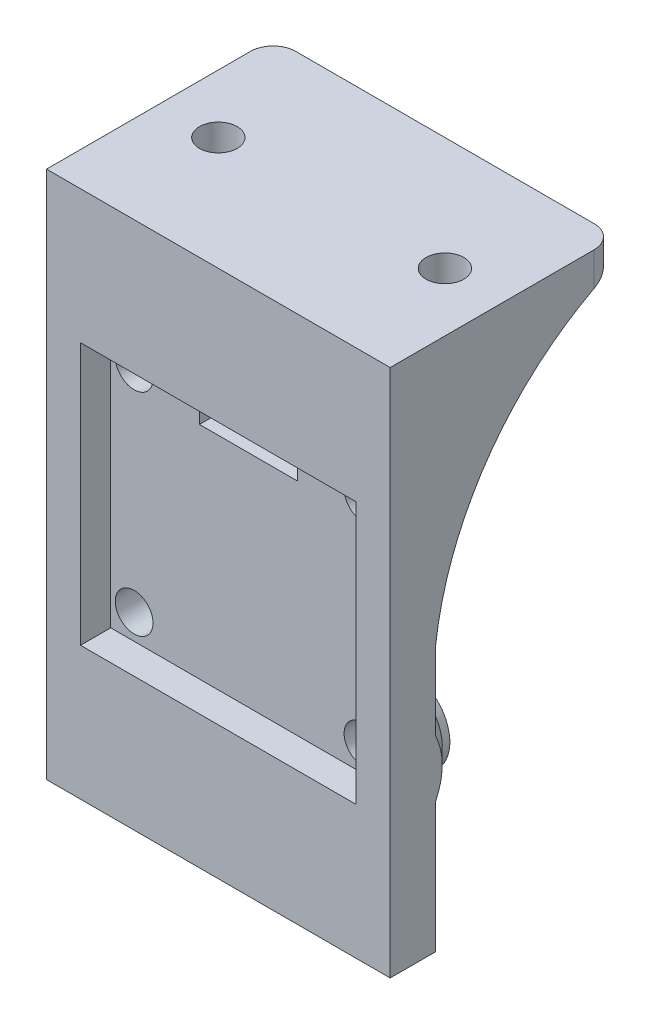
SolidWorks part; units mm, degrees
material "ABS"
ref_plane "Front Plane" through (0, 0, 0) normal (0, 0, 1) x (1, 0, 0)
ref_plane "Top Plane" through (0, 0, 0) normal (0, 1, 0) x (1, 0, 0)
ref_plane "Right Plane" through (0, 0, 0) normal (1, 0, 0) x (0, 0, -1)
sketch "Sketch1" plane through (0, 0, 0) normal (0, 0, 1) x (1, 0, 0)
  line L1 (-22.75, -35) -> (22.75, -35)
  line L2 (-22.75, -35) -> (-22.75, 35)
  line L3 (-22.75, 35) -> (22.75, 35)
  line L4 (22.75, -35) -> (22.75, 35)
  line L5 (-22.75, -35) -> (22.75, 35) construction
  line L6 (-22.75, 35) -> (22.75, -35) construction
  line L7 (-15.15, -14) -> (15.15, -14) construction
  line L8 (-15.15, -14) -> (-15.15, 14) construction
  line L9 (-15.15, 14) -> (15.15, 14) construction
  line L10 (15.15, -14) -> (15.15, 14) construction
  line L11 (-15.15, -14) -> (15.15, 14) construction
  line L12 (-15.15, 14) -> (15.15, -14) construction
  circle A0 centre (-15.15, 14) radius 2.5
  circle A1 centre (15.15, 14) radius 2.5
  circle A2 centre (15.15, -14) radius 2.5
  circle A3 centre (-15.15, -14) radius 2.5
  point P0 (0, 0)
  point P5 (0, 0)
  dimension "D5" = 5
  dimension "D1" = 70
  dimension "D2" = 45.5
  dimension "D3" = 28
  dimension "D4" = 30.3
extrude "Boss-Extrude1" add sketch "Sketch1" along normal blind 6
sketch "Sketch2" plane through (0, 0, 6) normal (0, 0, 1) x (1, 0, 0)
  line L1 (18.25, 17.35) -> (-18.25, 17.35)
  line L2 (18.25, 17.35) -> (18.25, -17.35)
  line L3 (18.25, -17.35) -> (-18.25, -17.35)
  line L4 (-18.25, 17.35) -> (-18.25, -17.35)
  line L5 (18.25, 17.35) -> (-18.25, -17.35) construction
  line L6 (18.25, -17.35) -> (-18.25, 17.35) construction
  point P0 (0, 0)
  dimension "D1" = 34.7
  dimension "D2" = 36.5
extrude "Cut-Extrude1" cut sketch "Sketch2" against normal blind 4
sketch "Sketch3" plane through (0, 0, 0) normal (1, 0, 0) x (0, 0, -1)
  line L0 (0, 35) -> (24, 35)
  line L1 (24, 35) -> (24, 32)
  line L2 (24, 32) -> (0, 32)
  line L3 (0, 35) -> (0, -35) construction
  line L4 (0, 32) -> (0, 35)
  dimension "D1" = 3
  dimension "D2" = 24
extrude "Boss-Extrude2" add sketch "Sketch3" along normal through all and the other way through all
sketch "Sketch4" plane through (-22.75, 0, 0) normal (-1, 0, 0) x (0, 0, 1)
  line L0 (-24, 32) -> (0, 32)
  line L1 (0, 32) -> (0, 0)
  arc A0 (-24, 32) -> (0, 0) centre (-39.7128, -4.7846) cw
  dimension "D1" = 40
extrude "Boss-Extrude3" add sketch "Sketch4" against normal blind 2
sketch "Sketch5" plane through (22.75, 0, 0) normal (1, 0, 0) x (0, 0, -1)
  line L2 (24, 32) -> (0, 32)
  line L3 (0, 32) -> (0, 0)
  line L4 (24, 32) -> (0, 32)
  line L5 (0, 32) -> (0, 0)
  arc A1 (24, 32) -> (0, 0) centre (39.7128, -4.7846) ccw
  arc A2 (24, 32) -> (0, 0) centre (39.7128, -4.7846) ccw
  dimension "D1" = 0
extrude "Boss-Extrude4" add sketch "Sketch5" against normal blind 2
sketch "Sketch6" plane through (0, 35, 0) normal (0, 1, 0) x (1, 0, 0)
  line L0 (15, 9) -> (-15, 9) construction
  line L3 (0, 0) -> (0, 9) construction
  circle A0 centre (-15, 9) radius 2.5
  circle A1 centre (15, 9) radius 2.5
  point P3 (0, 9)
  dimension "D3" = 5
  dimension "D1" = 9
  dimension "D2" = 30
extrude "Cut-Extrude2" cut sketch "Sketch6" against normal blind 6
fillet "Fillet1" radius 3 2 edges at (-22.75, 33.5, -24) (22.75, 33.5, -24)
sketch "Sketch7" plane through (0, 32, 0) normal (0, -1, 0) x (1, 0, 0)
  circle A2 centre (15, -9) radius 2.5 construction
  circle A3 centre (-15, -9) radius 2.5 construction
  circle A4 centre (15, -9) radius 2.5
  circle A5 centre (-15, -9) radius 2.5
  circle A6 centre (-15, -9) radius 5.5
  circle A7 centre (15, -9) radius 5.5
  dimension "D1" = 3
extrude "Boss-Extrude5" add sketch "Sketch7" along normal blind 3
sketch "Sketch8" plane through (0, 0, 0) normal (0, 0, -1) x (-1, 0, 0)
  circle A0 centre (-15.15, -14) radius 2.5 construction
  circle A1 centre (15.15, -14) radius 2.5 construction
  circle A2 centre (15.15, 14) radius 2.5 construction
  circle A3 centre (-15.15, 14) radius 2.5 construction
  circle A4 centre (-15.15, -14) radius 2.5
  circle A5 centre (15.15, -14) radius 2.5
  circle A6 centre (15.15, 14) radius 2.5
  circle A7 centre (-15.15, 14) radius 2.5
  circle A8 centre (-15.15, 14) radius 5.5
  circle A9 centre (15.15, 14) radius 5.5
  circle A10 centre (15.15, -14) radius 5.5
  circle A11 centre (-15.15, -14) radius 5.5
  dimension "D1" = 3
extrude "Boss-Extrude6" add sketch "Sketch8" along normal blind 4
chamfer "Chamfer1" distance 3 angle 45 6 edges at (-20.65, 14, 0) (-20.65, -14, 0) (-15, 32, -3.5) (15, 32, -3.5) (9.65, 14, 0) (9.65, -14, 0)
sketch "Sketch10" plane through (0, 0, 2) normal (0, 0, 1) x (1, 0, 0)
  line L1 (-6.5, 11.85) -> (6.5, 11.85)
  line L2 (-6.5, 11.85) -> (-6.5, 17.35)
  line L3 (-6.5, 17.35) -> (6.5, 17.35)
  line L4 (6.5, 11.85) -> (6.5, 17.35)
  line L5 (18.25, 17.35) -> (-18.25, 17.35) construction
  line L6 (-18.25, 17.35) -> (0, 11.85) construction
  line L7 (0, 11.85) -> (18.25, 17.35) construction
  line L8 (18.25, 17.35) -> (-18.25, 17.35) construction
  dimension "D1" = 5.5
  dimension "D2" = 13
extrude "Cut-Extrude3" cut sketch "Sketch10" against normal blind 10
chamfer "Chamfer3" distance 1 angle 45 1 edges at (0, 32, 0)
